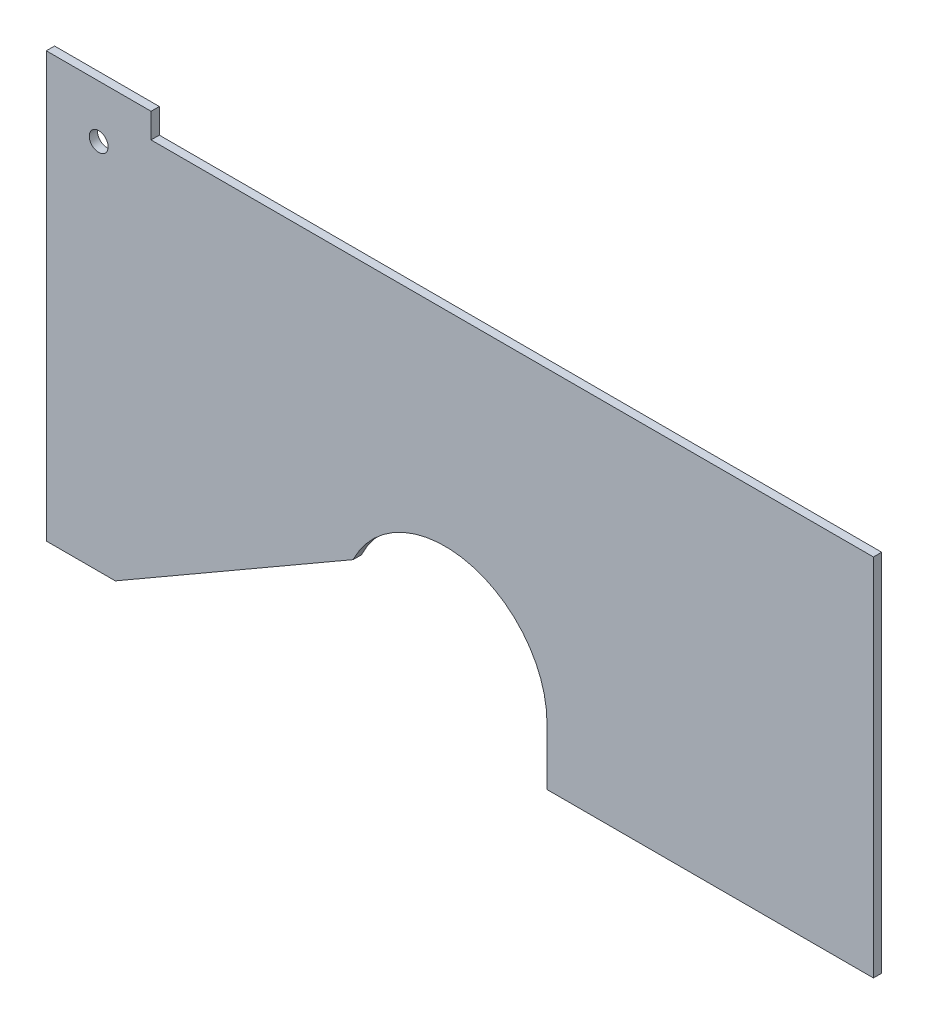
SolidWorks part; units mm, degrees
ref_plane "Front Plane" through (0, 0, 0) normal (0, 0, 1) x (1, 0, 0)
ref_plane "Top Plane" through (0, 0, 0) normal (0, 1, 0) x (1, 0, 0)
ref_plane "Right Plane" through (0, 0, 0) normal (1, 0, 0) x (0, 0, -1)
sketch "Sketch2" plane through (0, 0, 0) normal (0, 0, 1) x (1, 0, 0)
  line L0 (25.0304, 0) -> (111.2865, 49.8)
  line L1 (0, 0) -> (25.0304, 0)
  line L2 (0, 0) -> (0, 154)
  line L4 (300, 0) -> (300, 145)
  line L5 (181.6, 33.7) -> (181.6, 0)
  line L6 (181.6, 0) -> (300, 0)
  line L7 (19, 135) -> (19, 164.3674) construction
  line L11 (38, 145) -> (300, 145)
  line L12 (0, 154) -> (19, 154)
  line L13 (19, 154) -> (38, 154)
  line L14 (38, 154) -> (38, 145)
  line L15 (19, 135) -> (50019, 135) construction
  line L20 (19, 135) -> (19, -49865) construction
  circle A0 centre (19, 135) radius 3.425
  arc A1 (181.6, 33.7) -> (111.2865, 49.8) centre (144.6, 33.7) ccw
  point P19 (19, 154)
  dimension "D3" = 135
  dimension "D4" = 19
  dimension "D5" = 6.85
  dimension "D6" = 74
  dimension "D7" = 155.4
  dimension "D8" = 33.7
  dimension "D1" = 300
  dimension "D2" = 154
  dimension "D9" = 30
  dimension "D10" = 99.6
  dimension "D11" = 19
extrude "Boss-Extrude2" add sketch "Sketch2" along normal blind 3
sketch "Sketch3" plane through (0, 0, 3) normal (0, 0, 1) x (1, 0, 0)
  line L0 (300, 0) -> (300, 145) construction
  line L1 (181.6, 0) -> (300, 0)
  line L2 (181.6, 0) -> (181.6, 12.75)
  line L3 (181.6, 12.75) -> (300, 12.75)
  line L4 (300, 0) -> (300, 12.75)
  dimension "D1" = 12.75
extrude "Cut-Extrude1" cut sketch "Sketch3" against normal through all
sketch "Sketch4" plane through (0, 0, 3) normal (0, 0, 1) x (1, 0, 0)
  line L0 (19, 135) -> (19, -49865) construction
  line L1 (19, 135) -> (-49981, 135) construction
